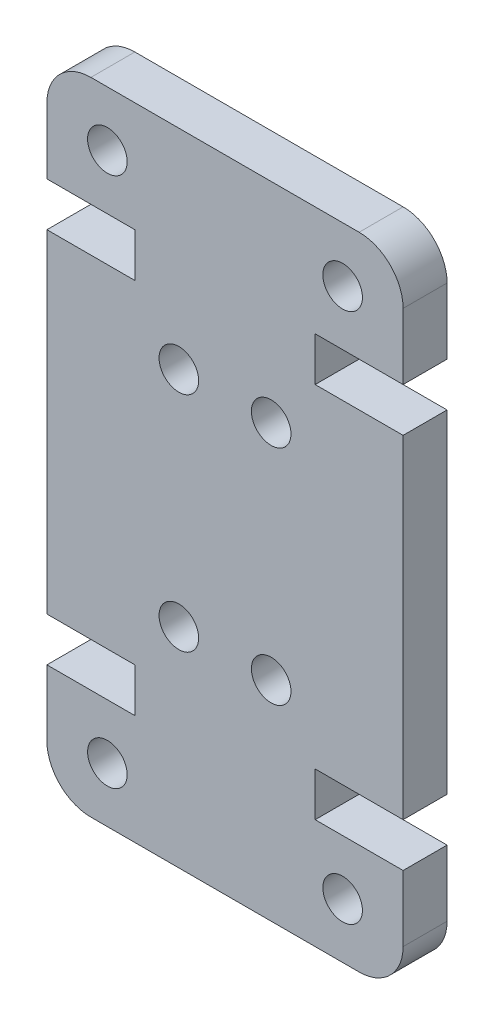
SolidWorks part; units mm, degrees
ref_plane "Front Plane" through (0, 0, 0) normal (0, 0, 1) x (1, 0, 0)
ref_plane "Top Plane" through (0, 0, 0) normal (0, 1, 0) x (1, 0, 0)
ref_plane "Right Plane" through (0, 0, 0) normal (1, 0, 0) x (0, 0, -1)
sketch "Sketch1" plane through (0, 0, 0) normal (0, 0, 1) x (1, 0, 0)
  line L0 (0, 22.14) -> (0, 7)
  line L1 (16.2, 2) -> (16.2, 5)
  line L2 (12.2, 5) -> (16.2, 5)
  line L3 (2, 0) -> (14.2, 0)
  line L4 (16.2, 7) -> (12.2, 7)
  line L5 (12.2, 7) -> (12.2, 5)
  line L6 (16.2, 22.14) -> (16.2, 7)
  line L7 (4, 7) -> (4, 5)
  line L8 (0, 27.14) -> (0, 24.14)
  line L9 (4, 24.14) -> (0, 24.14)
  line L10 (0, 7) -> (4, 7)
  line L11 (0, 22.14) -> (4, 22.14)
  line L12 (4, 5) -> (0, 5)
  line L13 (4, 22.14) -> (4, 24.14)
  line L14 (12.2, 22.14) -> (12.2, 24.14)
  line L15 (16.2, 22.14) -> (12.2, 22.14)
  line L16 (0, 2) -> (0, 5)
  line L17 (2, 29.14) -> (14.2, 29.14)
  line L18 (12.2, 24.14) -> (16.2, 24.14)
  line L19 (16.2, 27.14) -> (16.2, 24.14)
  line L20 (8.1, 29.14) -> (8.1, 0) construction
  line L21 (0, 14.57) -> (16.2, 14.57) construction
  circle A0 centre (13.45, 2.5) radius 0.9
  circle A1 centre (10.2, 9.5) radius 0.9
  arc A2 (16.2, 2) -> (14.2, 0) centre (14.2, 2) cw
  circle A3 centre (2.75, 26.64) radius 0.9
  circle A4 centre (6, 19.64) radius 0.9
  arc A5 (0, 2) -> (2, 0) centre (2, 2) ccw
  arc A6 (0, 27.14) -> (2, 29.14) centre (2, 27.14) cw
  circle A7 centre (6, 9.5) radius 0.9
  arc A8 (16.2, 27.14) -> (14.2, 29.14) centre (14.2, 27.14) ccw
  circle A9 centre (2.75, 2.5) radius 0.9
  circle A10 centre (10.2, 19.64) radius 0.9
  circle A11 centre (13.45, 26.64) radius 0.9
  point P15 (8.1, 14.57)
  dimension "D1" = 1.8
  dimension "D2" = 2
  dimension "D3" = 2.75
  dimension "D4" = 6
  dimension "D5" = 8.1
  dimension "D6" = 2.5
  dimension "D9" = 9.5
  dimension "D10" = 14.57
  dimension "D7" = 5
extrude "Boss-Extrude1" add sketch "Sketch1" along normal blind 2
equation "\"D5@Sketch1\"= \"fingerWidth@parametersSketch@prostheticParameters.SLDPRT\" / 2'PIP width"
equation "\"D10@Sketch1\"= ( \"HL@parametersSketch@prostheticParameters.SLDPRT\" * 0.244 - 4 - 12 ) / 2 'PIP length - Sil.Sht PIP - Sil. Sht MIP"
equation "\"D1@Sketch1\"= 1.5 + \"tol1@parametersSketch@prostheticParameters.SLDPRT\""
